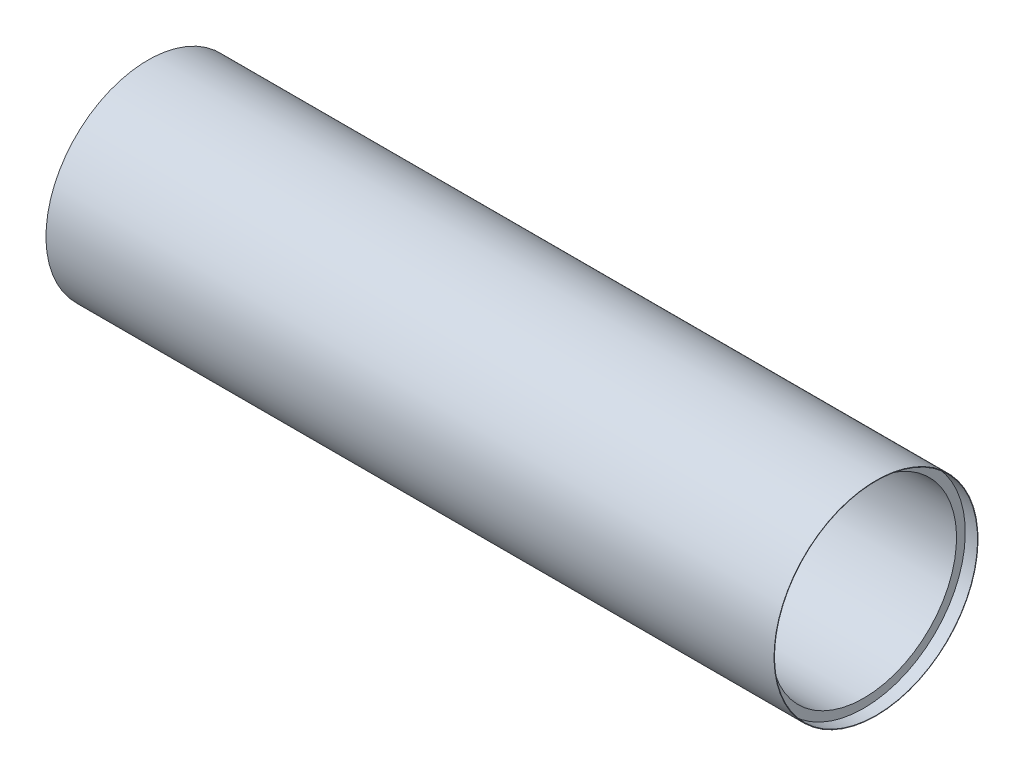
SolidWorks part; units mm, degrees
material "Hexcel AS4C (3000 Filaments)"
ref_plane "Front" through (0, 0, 0) normal (0, 0, 1) x (1, 0, 0)
ref_plane "Top" through (0, 0, 0) normal (0, 1, 0) x (1, 0, 0)
ref_plane "Right" through (0, 0, 0) normal (1, 0, 0) x (0, 0, -1)
sketch "Sketch1" plane through (0, 0, 0) normal (0, 0, 1) x (1, 0, 0)
  line L0 (39.1463, 83.9724) -> (49.3063, 83.9724)
  line L1 (49.3063, 83.9724) -> (49.3063, 76.7334)
  line L2 (49.3063, 76.7334) -> (631.0425, 76.7334)
  line L3 (631.0425, 76.7334) -> (631.0425, 83.9724)
  line L4 (631.0425, 83.9724) -> (641.2025, 83.9724)
  line L5 (641.2025, 83.9724) -> (641.2025, 84.3534)
  line L6 (641.2025, 84.3534) -> (39.1463, 84.3534)
  line L7 (39.1463, 84.3534) -> (39.1463, 83.9724)
  line L8 (0, 0) -> (134.0356, 0) construction
  dimension "D1" = 76.7334
  dimension "D2" = 0.381
  dimension "D3" = 10.16
  dimension "D4" = 10.16
  dimension "D5" = 581.7362
  dimension "D6" = 84.3534
  dimension "D7" = 0.381
revolve "Revolve1" add sketch "Sketch1" angle 360 about L8 region at (340.1744, 80.5497, 0)
